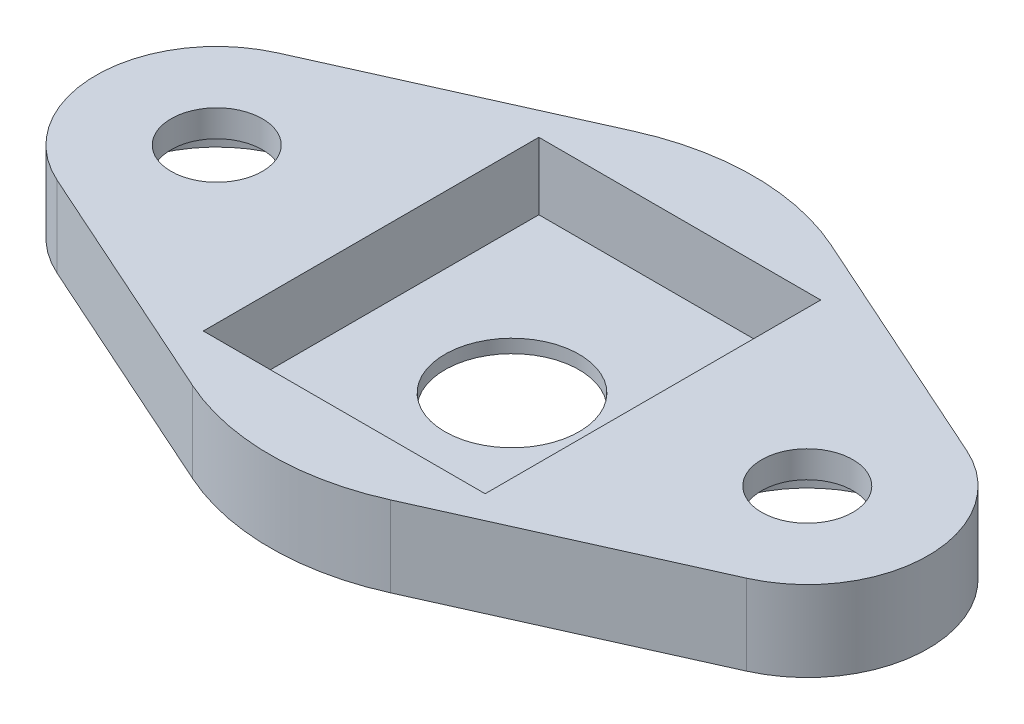
SolidWorks part; units mm, degrees
ref_plane "Front Plane" through (0, 0, 0) normal (0, 0, 1) x (1, 0, 0)
ref_plane "Top Plane" through (0, 0, 0) normal (0, 1, 0) x (1, 0, 0)
ref_plane "Right Plane" through (0, 0, 0) normal (1, 0, 0) x (0, 0, -1)
sketch "Sketch1" plane through (0, 0, 0) normal (0, 1, 0) x (1, 0, 0)
  line L0 (-11, 0) -> (11, 0) construction
  line L1 (-3.6818, 8.2124) -> (-12.8409, 4.1062)
  line L3 (-12.8409, -4.1062) -> (-3.6818, -8.2124)
  line L5 (12.8409, -4.1062) -> (3.6818, -8.2124)
  line L7 (12.8409, 4.1062) -> (3.6818, 8.2124)
  line L10 (-5.25, 6.25) -> (5.25, 6.25)
  line L11 (-5.25, 6.25) -> (-5.25, -6.25)
  line L12 (-5.25, -6.25) -> (5.25, -6.25)
  line L13 (5.25, 6.25) -> (5.25, -6.25)
  circle A22 centre (0, 0) radius 9
  circle A23 centre (0, 0) radius 2.5
  circle A24 centre (-11, 0) radius 1.7
  circle A25 centre (11, 0) radius 1.7
  circle A30 centre (-11, 0) radius 4.5
  circle A31 centre (11, 0) radius 4.5
  circle A32 centre (-11, 0) radius 4.15
  circle A33 centre (11, 0) radius 4.15
  point P16 (0, 6.25)
  point P17 (-5.25, 0)
  point P59 (0, 0)
  dimension "D3" = 9
  dimension "D4" = 9
  dimension "D5" = 8.3
  dimension "D6" = 8.3
  dimension "D7" = 10.5
  dimension "D8" = 12.5
  dimension "D18" = 5
  dimension "D19" = 18
  dimension "D20" = 3.4
  dimension "D21" = 3.4
  dimension "D22" = 22
extrude "Boss-Extrude1" add sketch "Sketch1" along normal blind 3 contours A30 A22 L1 | A30 L3 A22 | A31 A22 L5 | A31 L7 A22 | A24 | A23 L0 | L0 A23 | A25 | A30 | A22 | A31 region at (-12.6519, 0, 0) region at (-8.4253, 0, -5.3428) region at (-8.4253, 0, 5.3428) region at (0, 0, -1.061) region at (0, 0, 1.061) region at (8.4253, 0, -5.3428) region at (8.4253, 0, 5.3428) region at (11, 0, -1.6519)
extrude "Cut-Extrude1" cut sketch "Sketch1<11>" along normal blind 2 contours A24 A22 A32 | A22 A33 A25 | A22 L0 A32 | L0 A22 A32 | A33 L0 A22 | L0 A33 A22 region at (-8.0056, 0, 1.2412) region at (-8.0056, 0, -1.2412) region at (-8.9537, 0, 1.6641) region at (12.7466, 0, -3.6463) region at (8.0056, 0, -1.2412) region at (8.0056, 0, 1.2412)
sketch "Sketch1<11>" plane through (0, 0, 0) normal (0, 1, 0) x (1, 0, 0) same geometry as "Sketch1"
extrude "Cut-Extrude2" cut sketch "Sketch1<12>" against normal blind 2.5 from surface contours L11 L0 A23 L13 L10 | L0 L11 L12 L13 A23 region at (0, 0, -3.4881) region at (0, 0, 3.4881) starting at face at (0, 3, 0)
sketch "Sketch1<12>" plane through (0, 0, 0) normal (0, 1, 0) x (1, 0, 0) same geometry as "Sketch1"
